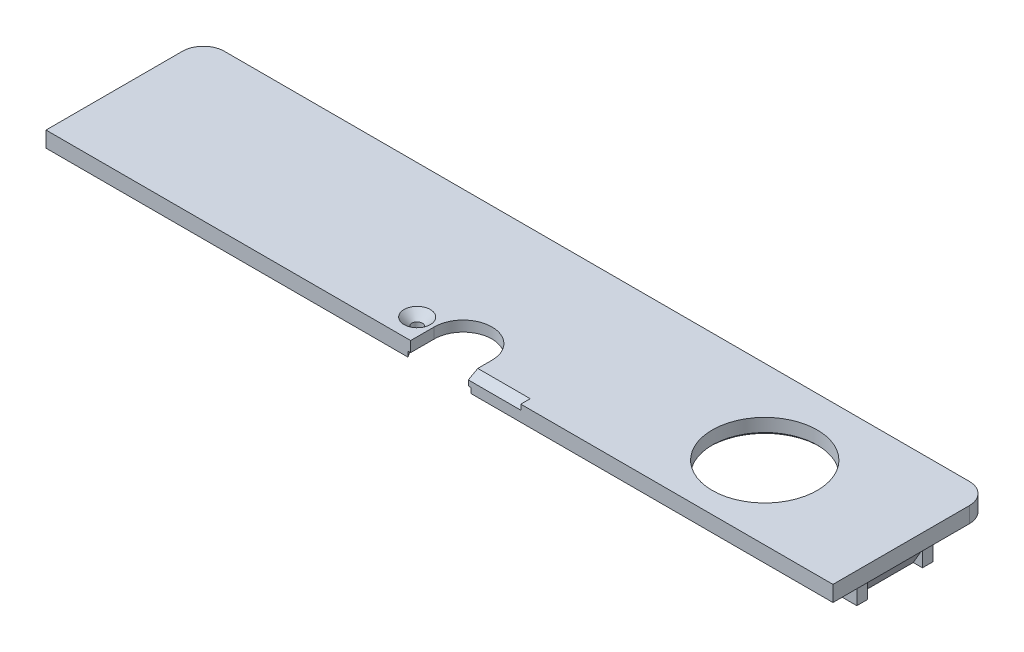
SolidWorks part; units mm, degrees
material "PLA Filament Green"
ref_plane "Alzado" through (0, 0, 0) normal (0, 0, 1) x (1, 0, 0)
ref_plane "Planta" through (0, 0, 0) normal (0, 1, 0) x (1, 0, 0)
ref_plane "Vista lateral" through (0, 0, 0) normal (1, 0, 0) x (0, 0, -1)
sketch "Croquis1" plane through (0, 0, 0) normal (0, 1, 0) x (1, 0, 0)
  line L0 (-75, 15) -> (75, -15) construction
  line L1 (-71, 15) -> (71, 15)
  line L2 (-75, 11) -> (-75, -15)
  line L3 (-75, -15) -> (75, -15)
  line L4 (75, 11) -> (75, -15)
  arc A0 (71, 15) -> (75, 11) centre (71, 11) cw
  arc A1 (-71, 15) -> (-75, 11) centre (-71, 11) ccw
  point P7 (75, 15)
  dimension "D3" = 4
  dimension "D1" = 150
  dimension "D2" = 30
extrude "Saliente-Extruir1" add sketch "Croquis1" along normal blind 3 contours L1 A0 L4 L3 L2 A1
sketch "Croquis2" plane through (0, 3, 0) normal (0, 1, 0) x (1, 0, 0)
  line L0 (-5.5, -10.5) -> (-5.5, -15)
  line L1 (0, -15) -> (0, 0) construction
  line L2 (-75, -15) -> (75, -15) construction
  line L3 (-5.5, -15) -> (5.5, -15)
  line L4 (5.5, -15) -> (5.5, -10.5)
  arc A0 (5.5, -10.5) -> (-5.5, -10.5) centre (0, -10.5) ccw
  dimension "D1" = 11
  dimension "D2" = 4.5
extrude "Cortar-Extruir1" cut sketch "Croquis2" against normal up to next contours A0 L0 L3 L4
sketch "Croquis3" plane through (0, 0, 0) normal (0, -1, 0) x (1, 0, 0)
  circle A0 centre (0, 10.5) radius 7.5
  arc A1 (-5.5, 10.5) -> (5.5, 10.5) centre (0, 10.5) ccw construction
  dimension "D1" = 15
extrude "Cortar-Extruir2" cut sketch "Croquis3" against normal blind 1
sketch "Croquis4" plane through (0, 3, 0) normal (0, 1, 0) x (1, 0, 0)
  line L0 (75, 11) -> (75, -15) construction
  line L1 (-71, 15) -> (71, 15) construction
  circle A0 centre (48, -1) radius 10
  dimension "D1" = 20
  dimension "D2" = 27
  dimension "D3" = 16
extrude "Cortar-Extruir3" cut sketch "Croquis4" against normal through all
chamfer "Chaflán1" distance 0.5 angle 45 1 edges at (48, 0, 11)
sketch "Sketch1" plane through (0, 3, 0) normal (0, 1, 0) x (1, 0, 0)
  line L1 (-75, -15) -> (-5.5, -15) construction
  circle A0 centre (-8.75, -10.5) radius 1
  arc A1 (5.5, -10.5) -> (-5.5, -10.5) centre (0, -10.5) ccw construction
  dimension "D1" = 2
  dimension "D2" = 8.75
  dimension "D3" = 4.5
extrude "Cut-Extrude1" cut sketch "Sketch1" against normal blind 10 contours A0
sketch "Croquis5" plane through (0, 0, 0) normal (0, -1, 0) x (1, 0, 0)
  line L0 (-71.8, 7.25) -> (-68.05, 7.25)
  line L2 (-70.05, 5.25) -> (-70.05, -5.25)
  line L3 (-68.05, -7.25) -> (-71.8, -7.25)
  line L4 (-68.05, 7.25) -> (-68.05, -7.25)
  line L5 (-71.8, -7.25) -> (-71.8, -5.25)
  line L6 (-71.8, 7.25) -> (-71.8, 5.25)
  line L7 (-71.8, 5.25) -> (-70.05, 5.25)
  line L8 (-70.05, -5.25) -> (-71.8, -5.25)
  line L9 (-70.05, 0) -> (-68.05, 0) construction
  line L10 (-71, -15) -> (71, -15) construction
  line L14 (-75, -11) -> (-75, 15) construction
  line L21 (-71.8, -7.25) -> (-75, -7.25) construction
  dimension "D1" = 10.5
  dimension "D2" = 2
  dimension "D3" = 1.75
  dimension "D4" = 3.2
  dimension "D5" = 9.75
extrude "Saliente-Extruir2" add sketch "Croquis5" along normal blind 6
sketch "Croquis6" plane through (0, 0, 5.25) normal (0, 0, -1) x (-1, 0, 0)
  line L0 (71.8, -6) -> (71.8, 0) construction
  line L1 (71.8, -3) -> (70.05, -6)
  line L2 (70.05, 0) -> (71.8, 0)
  line L5 (70.05, 0) -> (70.05, -6)
  line L6 (75, 0) -> (6, 0) construction
  arc A0 (71.8, 0) -> (71.8, -3) centre (73.1229, -1.5) ccw
  dimension "D1" = 3
  dimension "D2" = 2
extrude "Saliente-Extruir3" add sketch "Croquis6" along normal up to surface (10.5 mm away) up to face at (-70.925, -3, -5.25)
mirror "Simetría1" about plane through (0, 0, 0) normal (1, 0, 0) of "Saliente-Extruir3", "Saliente-Extruir2"
sketch "Sketch5" plane through (0, 0, 0) normal (1, 0, 0) x (0, 0, -1)
  line L0 (11.9, 0) -> (11.9, -6)
  line L1 (11, 0) -> (15, 0) construction
  line L2 (11.9, -6) -> (7.9, 0)
  line L3 (11, 0) -> (-15, 0) construction
  line L4 (7.9, 0) -> (11.9, 0)
  line L5 (15, 3) -> (15, 0) construction
  dimension "D1" = 3.1
  dimension "D2" = 6
  dimension "D3" = 4
extrude "Boss-Extrude2" add sketch "Sketch5" along normal blind 5 and the other way blind 5
chamfer "Chamfer1" distance 1.5 angle 45 1 edges at (-8.75, 3, 11.5)
sketch "Sketch7" plane through (5.5, 0, 0) normal (-1, 0, 0) x (0, 0, 1)
  line L0 (13.2, 3) -> (15, 2)
  line L1 (15, 3) -> (10.5, 3) construction
  line L2 (15, 1) -> (15, 3) construction
  line L3 (15, 2) -> (15, 3)
  line L4 (15, 3) -> (13.2, 3)
  dimension "D1" = 1.8
  dimension "D2" = 1
extrude "Cut-Extrude3" cut sketch "Sketch7" against normal blind 10 contours L4 L0 L3
